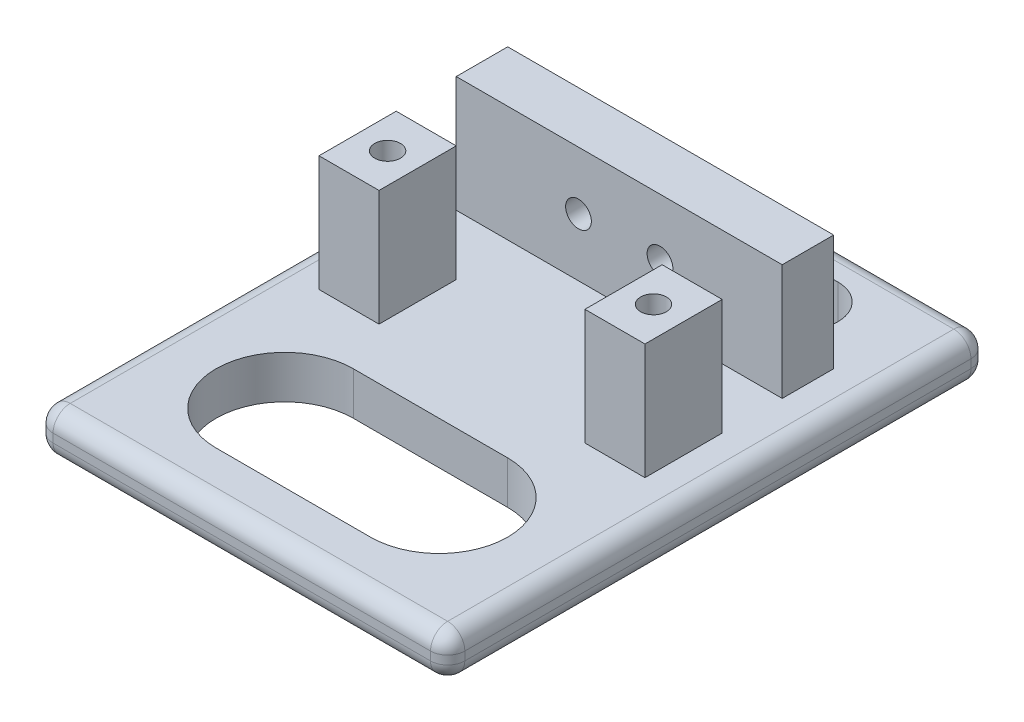
SolidWorks part; units mm, degrees
material "PET"
ref_plane "Alzado" through (0, 0, 0) normal (0, 0, 1) x (1, 0, 0)
ref_plane "Planta" through (0, 0, 0) normal (0, 1, 0) x (1, 0, 0)
ref_plane "Vista lateral" through (0, 0, 0) normal (1, 0, 0) x (0, 0, -1)
sketch "Croquis1" plane through (0, 0, 0) normal (0, 1, 0) x (1, 0, 0)
  line L0 (-9, -17.5) -> (9, -17.5) construction
  line L1 (-24, -31.5) -> (24, -31.5)
  line L2 (-24, -31.5) -> (-24, 31.5)
  line L3 (-24, 31.5) -> (24, 31.5)
  line L4 (24, -31.5) -> (24, 31.5)
  line L5 (-24, -31.5) -> (24, 31.5) construction
  line L6 (-24, 31.5) -> (24, -31.5) construction
  line L7 (-9, -9.5) -> (9, -9.5)
  line L8 (-9, -25.5) -> (9, -25.5)
  line L9 (-10.5, 23.5) -> (10.5, 23.5) construction
  line L10 (-10.5, 27.5) -> (10.5, 27.5)
  line L11 (-10.5, 19.5) -> (10.5, 19.5)
  arc A0 (-9, -9.5) -> (-9, -25.5) centre (-9, -17.5) ccw
  arc A1 (9, -25.5) -> (9, -9.5) centre (9, -17.5) ccw
  arc A2 (-10.5, 27.5) -> (-10.5, 19.5) centre (-10.5, 23.5) ccw
  arc A3 (10.5, 19.5) -> (10.5, 27.5) centre (10.5, 23.5) ccw
  point P0 (0, 0)
  point P8 (0, -17.5)
  point P17 (0, 23.5)
  dimension "D4" = 8
  dimension "D7" = 8
  dimension "D1" = 63
  dimension "D2" = 48
  dimension "D3" = 14
  dimension "D5" = 18
  dimension "D6" = 21
  dimension "D8" = 8
extrude "Saliente-Extruir1" add sketch "Croquis1" against normal blind 5
sketch "Croquis2" plane through (0, 0, 0) normal (0, 1, 0) x (1, 0, 0)
  line L0 (-24, -31.5) -> (24, -31.5) construction
  line L1 (12, 5.5) -> (19, 5.5)
  line L2 (12, 5.5) -> (12, -3.5)
  line L3 (12, -3.5) -> (19, -3.5)
  line L4 (19, 5.5) -> (19, -3.5)
  line L9 (0, -55) -> (0, 55) construction
  line L10 (-12, -3.5) -> (-19, -3.5)
  line L11 (-19, 5.5) -> (-19, -3.5)
  line L12 (-12, 5.5) -> (-19, 5.5)
  line L13 (-12, 5.5) -> (-12, -3.5)
  line L15 (19, 12.5) -> (-19, 12.5)
  line L16 (19, 12.5) -> (19, 18.5)
  line L17 (19, 18.5) -> (-19, 18.5)
  line L18 (-19, 12.5) -> (-19, 18.5)
  point P4 (15.5, -3.5)
  dimension "D1" = 7
  dimension "D2" = 9
  dimension "D3" = 15.5
  dimension "D4" = 28
  dimension "D5" = 38
  dimension "D6" = 6
  dimension "D7" = 7
extrude "Saliente-Extruir2" add sketch "Croquis2" along normal blind 13.5
sketch "Croquis3" plane through (0, 0, -12.5) normal (0, 0, 1) x (1, 0, 0)
  line L0 (19, 13.5) -> (19, 0) construction
  line L1 (-19, 13.5) -> (19, 13.5) construction
  line L2 (0, -55) -> (0, 55) construction
  circle A0 centre (4.75, 6.75) radius 1.5
  circle A1 centre (-4.75, 6.75) radius 1.5
  dimension "D1" = 3
  dimension "D2" = 14.25
  dimension "D3" = 6.75
extrude "Cortar-Extruir1" cut sketch "Croquis3" against normal up to next
fillet "Redondeo1" radius 2 12 edges at (0, -5, -31.5) (0, 0, -31.5) (-24, -5, 0) (-24, -2.5, -31.5) (-24, 0, 0) (0, -5, 31.5) (-24, -2.5, 31.5) (0, 0, 31.5) (24, -2.5, -31.5) (24, -5, 0) (24, -2.5, 31.5) (24, 0, 0)
sketch "Croquis4" plane through (0, 13.5, 0) normal (0, 1, 0) x (1, 0, 0)
  line L0 (-19, 5.5) -> (-12, -3.5) construction
  line L1 (19, 5.5) -> (12, -3.5) construction
  circle A0 centre (-15.5, 1) radius 1.5
  circle A1 centre (15.5, 1) radius 1.5
  dimension "D1" = 3
extrude "Cortar-Extruir2" cut sketch "Croquis4" against normal blind 10
